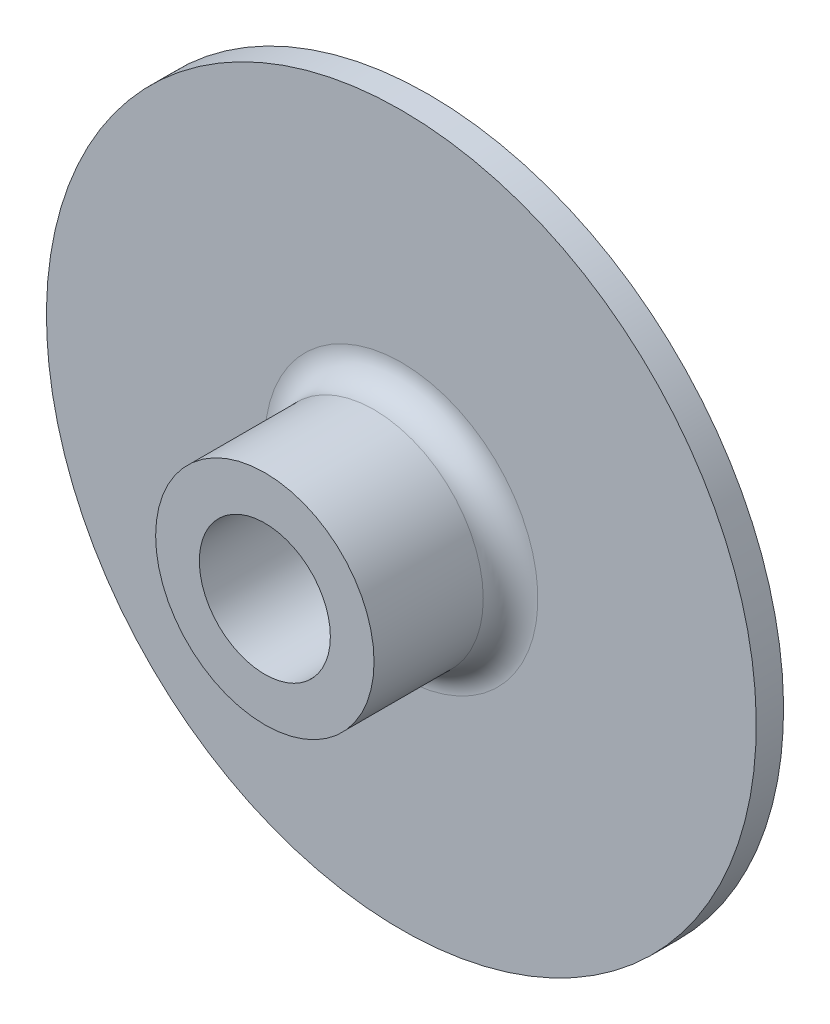
SolidWorks part; units mm, degrees
material "AISI 1020"
ref_plane "Front Plane" through (0, 0, 0) normal (0, 0, 1) x (1, 0, 0)
ref_plane "Top Plane" through (0, 0, 0) normal (0, 1, 0) x (1, 0, 0)
ref_plane "Right Plane" through (0, 0, 0) normal (1, 0, 0) x (0, 0, -1)
sketch "Sketch2" plane through (0, 0, 0) normal (1, 0, 0) x (0, 0, -1)
  line L2 (0, 0) -> (0, 41.275)
  line L3 (0, 41.275) -> (-3.175, 41.275)
  line L4 (-3.175, 12.7) -> (-3.175, 41.275)
  line L5 (0, 0) -> (-19.05, 0)
  line L7 (-3.175, 12.7) -> (-19.05, 12.7)
  line L8 (-19.05, 0) -> (-19.05, 12.7)
  dimension "D1" = 19.05
  dimension "D2" = 41.275
  dimension "D3" = 3.175
  dimension "D4" = 12.7
revolve "Revolve1" add sketch "Sketch2" angle 360 about L5
sketch "Sketch3" plane through (0, 0, 19.05) normal (0, 0, 1) x (1, 0, 0)
  circle A0 centre (0, 0) radius 7.62
  circle A1 centre (0, 0) radius 34.925 construction
  circle A2 centre (-28.0086, 20.8632) radius 3.175
  dimension "D1" = 15.24
extrude "Cut-Extrude1" cut sketch "Sketch3" against normal through all
pattern_circular "CirPattern1" [suppressed] count 6 over 360 of bodies 105
fillet "Fillet1" radius 3.175 1 edges at (0, 12.7, 3.175)
other "DeleteFace2" face at (-28.0086, 17.6882, 3.175) and patch yes
